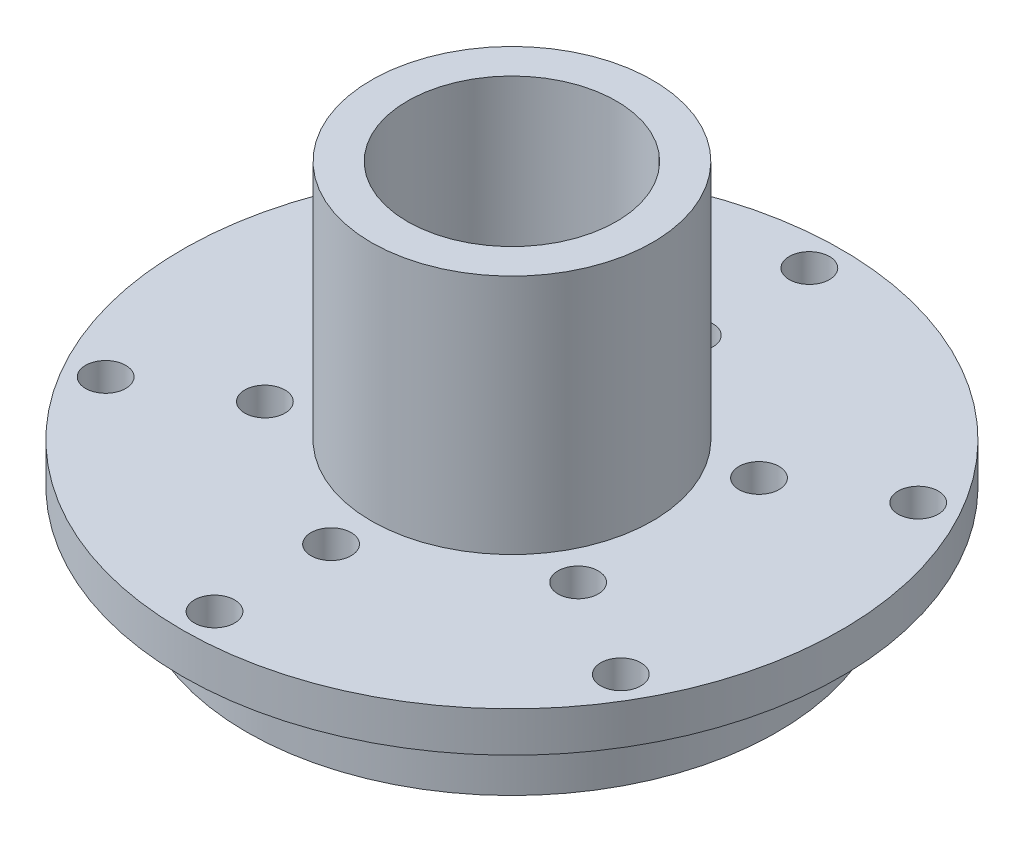
SolidWorks part; units mm, degrees
ref_plane "Front Plane" through (0, 0, 0) normal (0, 0, 1) x (1, 0, 0)
ref_plane "Top Plane" through (0, 0, 0) normal (0, 1, 0) x (1, 0, 0)
ref_plane "Right Plane" through (0, 0, 0) normal (1, 0, 0) x (0, 0, -1)
sketch "Sketch1" plane through (0, 0, 0) normal (0, 1, 0) x (1, 0, 0)
  circle A0 centre (0, 0) radius 33
  circle A1 centre (0, 0) radius 22.5 construction
  circle A2 centre (0, 0) radius 5
  circle A3 centre (0, 22.5) radius 2.5
  circle A4 centre (19.4856, 11.25) radius 2.5
  circle A5 centre (19.4856, -11.25) radius 2.5
  circle A6 centre (0, -22.5) radius 2.5
  circle A7 centre (-19.4856, -11.25) radius 2.5
  circle A8 centre (-19.4856, 11.25) radius 2.5
  point P19 (0, 0)
  dimension "D1" = 66
  dimension "D2" = 10
  dimension "D3" = 45
  dimension "D4" = 5
  dimension "D5" = 6
extrude "Boss-Extrude1" add sketch "Sketch1" along normal blind 10
sketch "Sketch2" plane through (0, 0, 0) normal (0, -1, 0) x (1, 0, 0)
  circle A0 centre (0, 0) radius 16
  dimension "D1" = 32
extrude "Cut-Extrude1" cut sketch "Sketch2" against normal blind 5
sketch "Sketch5" plane through (0, 10, 0) normal (0, 1, 0) x (1, 0, 0)
  circle A0 centre (0, 0) radius 13
  dimension "D1" = 26
extrude "Cut-Extrude2" cut sketch "Sketch5" against normal up to surface (5 mm away) up to face at (0, 5, -5)
sketch "Sketch6" plane through (0, 10, 0) normal (0, 1, 0) x (1, 0, 0)
  circle A0 centre (0, 0) radius 13
  circle A1 centre (0, 0) radius 17.5
  circle A2 centre (0, 0) radius 13 construction
  dimension "D1" = 35
extrude "Boss-Extrude2" add sketch "Sketch6" along normal blind 35
sketch "Sketch8" plane through (0, 10, 0) normal (0, 1, 0) x (1, 0, 0)
  circle A0 centre (0, 0) radius 41
  circle A2 centre (0, 22.5) radius 2.5
  circle A3 centre (-19.4856, 11.25) radius 2.5
  circle A4 centre (-19.4856, -11.25) radius 2.5
  circle A5 centre (0, -22.5) radius 2.5
  circle A6 centre (19.4856, -11.25) radius 2.5
  circle A7 centre (19.4856, 11.25) radius 2.5
  circle A8 centre (0, 22.5) radius 2.5 construction
  circle A9 centre (0, 0) radius 13
  circle A10 centre (0, 0) radius 13 construction
  circle A11 centre (0, 37) radius 2.5
  circle A12 centre (0, 0) radius 37 construction
  circle A13 centre (32.0429, 18.5) radius 2.5
  circle A14 centre (32.0429, -18.5) radius 2.5
  circle A15 centre (0, -37) radius 2.5
  circle A16 centre (-32.0429, -18.5) radius 2.5
  circle A17 centre (-32.0429, 18.5) radius 2.5
  point P29 (0, 0)
  point P30 (0, -37.5)
  point P40 (0, 0)
  dimension "D1" = 82
  dimension "D2" = 5
  dimension "D3" = 74
  dimension "D4" = 6
extrude "Boss-Extrude3" add sketch "Sketch8" along normal blind 5
